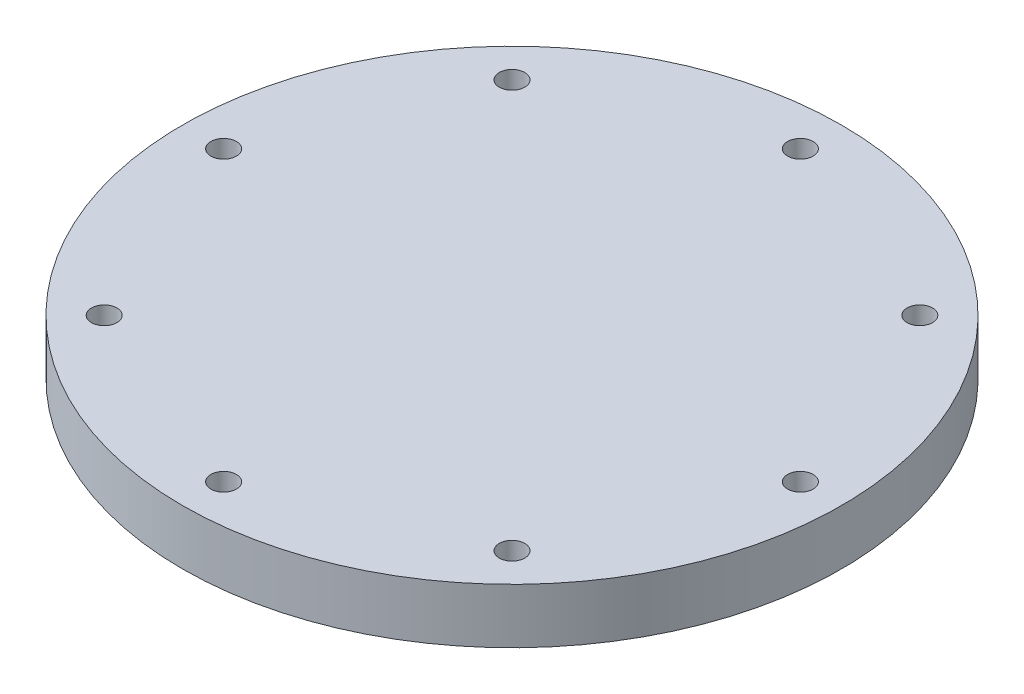
SolidWorks part; units mm, degrees
ref_plane "Front Plane" through (0, 0, 0) normal (0, 0, 1) x (1, 0, 0)
ref_plane "Top Plane" through (0, 0, 0) normal (0, 1, 0) x (1, 0, 0)
ref_plane "Right Plane" through (0, 0, 0) normal (1, 0, 0) x (0, 0, -1)
sketch "Sketch1" plane through (0, 0, 0) normal (0, 1, 0) x (1, 0, 0)
  circle A0 centre (0, 0) radius 38.1
  dimension "D1" = 76.2
extrude "Boss-Extrude1" add sketch "Sketch1" along normal blind 6.35
sketch "Sketch2" plane through (0, 0, 0) normal (0, -1, 0) x (1, 0, 0)
  circle A0 centre (0, 0) radius 33.3375
  circle A1 centre (0, 33.3375) radius 0.762
  dimension "D1" = 66.675
hole_wizard "CBORE for #4 Button Head Cap Screw1" positions "Sketch5" profile "Sketch4" counterbore size "#4" standard "ANSI Inch" end condition through all
sketch "Sketch5" plane through (0, 0, 0) normal (0, -1, 0) x (-1, 0, 0)
  point P0 (0, -33.3375)
sketch "Sketch4" plane through (0, 0, 33.3375) normal (1, 0, 0) x (0, 0, -1)
  line L0 (0, 0) -> (0, 6.35)
  line L1 (0, 6.35) -> (1.4732, 6.35)
  line L3 (1.4732, 6.35) -> (1.4732, 1.4986)
  line L4 (1.4732, 1.4986) -> (2.8575, 1.4986)
  line L5 (2.8575, 1.4986) -> (2.8575, 0)
  line L7 (2.8575, 0) -> (0, 0)
  line L11 (0, -6.35) -> (0, 107.95) construction
  dimension "Thru Hole Dia." = 2.9464
  dimension "Thru Hole Depth" = 6.35
  dimension "C'Bore Dia." = 5.715
  dimension "C'Bore Depth" = 1.4986
pattern_circular "CirPattern1" count 8 over 360 about axis through (0, 0, 0) along (0, 1, 0) of "CBORE for #4 Button Head Cap Screw1"
sketch "Sketch6" plane through (0, 6.35, 0) normal (0, 1, 0) x (1, 0, 0)
  circle A0 centre (0, 0) radius 28.575
  dimension "D1" = 57.15
